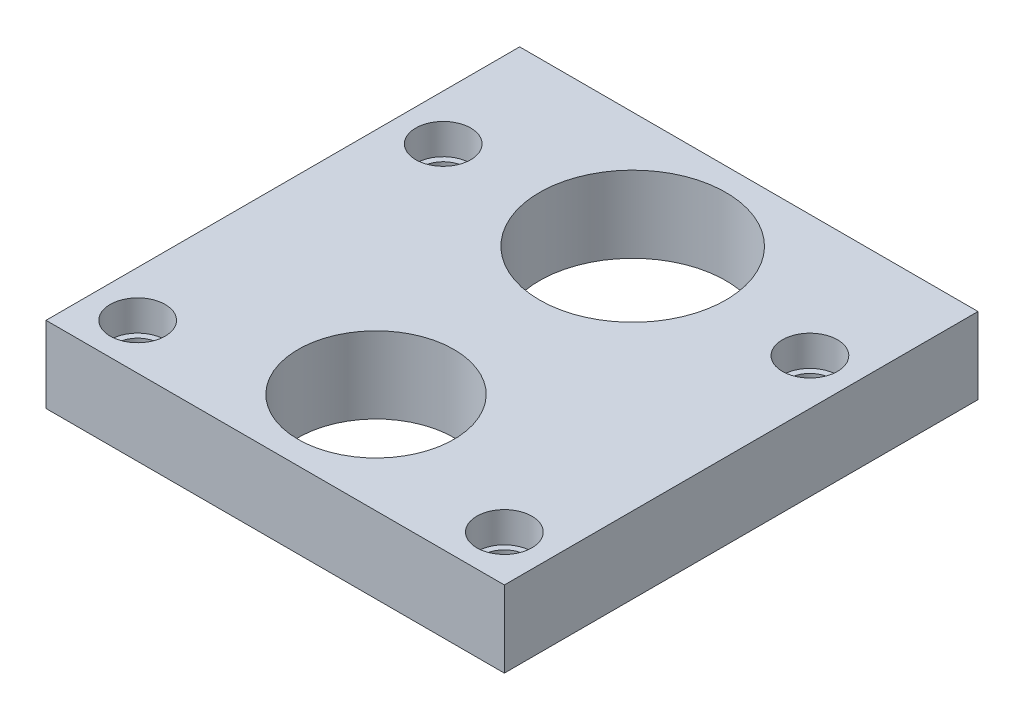
SolidWorks part; units mm, degrees
ref_plane "前视基准面" through (0, 0, 0) normal (0, 0, 1) x (1, 0, 0)
ref_plane "上视基准面" through (0, 0, 0) normal (0, 1, 0) x (1, 0, 0)
ref_plane "右视基准面" through (0, 0, 0) normal (1, 0, 0) x (0, 0, -1)
other "Configuration Table"
sketch "草图1" plane through (0, 0, 0) normal (0, 1, 0) x (1, 0, 0)
  line L0 (0, 7.5) -> (0, -8) construction
  line L1 (-7.5, 7.5) -> (7.5, 7.5)
  line L2 (-7.5, 7.5) -> (-7.5, -8)
  line L3 (-7.5, -8) -> (7.5, -8)
  line L4 (7.5, 7.5) -> (7.5, -8)
  line L5 (-7.5, 5) -> (7.5, 5) construction
  circle A1 centre (0, -4.7) radius 2.55
  circle A2 centre (0, 3.7) radius 3.05
  circle A3 centre (6, 3.5) radius 1.5
  circle A4 centre (-6, -6.5) radius 1.5
  circle A5 centre (-6, -6.5) radius 0.9
  circle A6 centre (-6, -6.5) radius 0.7
  circle A7 centre (6, 3.5) radius 0.9
  circle A8 centre (6, 3.5) radius 0.7
  circle A9 centre (-6, 3.5) radius 1.5
  circle A10 centre (-6, 3.5) radius 0.9
  circle A11 centre (-6, 3.5) radius 0.7
  circle A12 centre (6, -6.5) radius 1.5
  circle A13 centre (6, -6.5) radius 0.9
  circle A14 centre (6, -6.5) radius 0.7
  dimension "D2" = 5.1
  dimension "D5" = 6.1
  dimension "D8" = 3
  dimension "D9" = 1.8
  dimension "D10" = 1.4
  dimension "D3" = 8
  dimension "D4" = 8.4
  dimension "D6" = 15
  dimension "D7" = 5
  dimension "D11" = 7.5
  dimension "D12" = 4.7
extrude "凸台-拉伸1" add sketch "草图1" along normal blind 2.5 contours L2 L3 L4 L1 | A2 | A1
extrude "切除-拉伸2" cut sketch "草图1<4>" against normal blind 1 from surface contours A5 | A7 | A13 | A10 starting at face at (0, 2.5, 0.25)
sketch "草图1<4>" plane through (0, 0, 0) normal (0, 1, 0) x (1, 0, 0) same geometry as "草图1"
extrude "切除-拉伸3" cut sketch "草图1<5>" against normal through all from surface contours A6 | A8 | A11 | A14 starting at face at (-6, 2.5, -4.4)
sketch "草图1<5>" plane through (0, 0, 0) normal (0, 1, 0) x (1, 0, 0) same geometry as "草图1"
